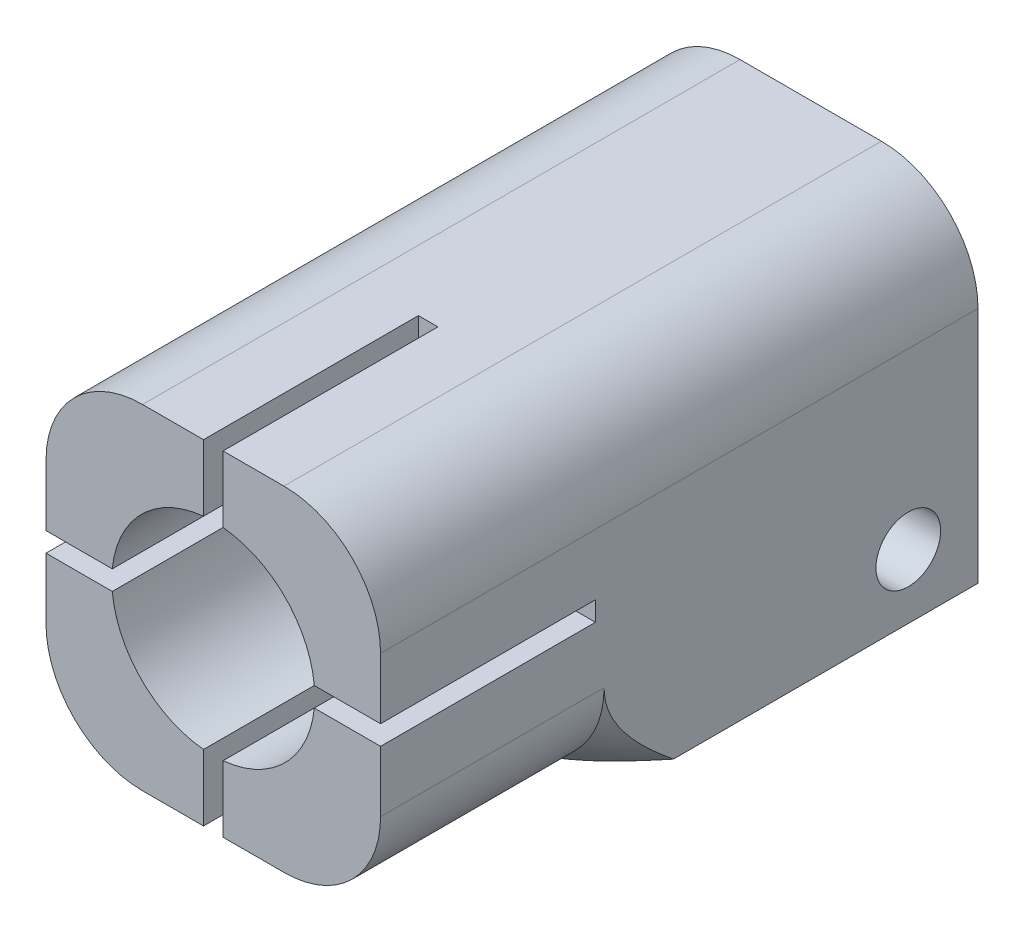
SolidWorks part; units mm, degrees
ref_plane "Front Plane" through (0, 0, 0) normal (0, 0, 1) x (1, 0, 0)
ref_plane "Top Plane" through (0, 0, 0) normal (0, 1, 0) x (1, 0, 0)
ref_plane "Right Plane" through (0, 0, 0) normal (1, 0, 0) x (0, 0, -1)
sketch "Sketch1" plane through (0, 0, 0) normal (0, 0, 1) x (1, 0, 0)
  line L1 (-3.55, 8.4) -> (3.55, 8.4)
  line L2 (-8.4, 3.55) -> (-8.4, -3.55)
  line L3 (-3.55, -8.4) -> (3.55, -8.4)
  line L4 (8.4, 3.55) -> (8.4, -3.55)
  line L5 (-8.4, 8.4) -> (8.4, -8.4) construction
  line L6 (-8.4, -8.4) -> (8.4, 8.4) construction
  arc A0 (3.55, 8.4) -> (8.4, 3.55) centre (3.55, 3.55) cw
  arc A1 (3.55, -8.4) -> (8.4, -3.55) centre (3.55, -3.55) ccw
  arc A2 (-8.4, -3.55) -> (-3.55, -8.4) centre (-3.55, -3.55) ccw
  arc A3 (-3.55, 8.4) -> (-8.4, 3.55) centre (-3.55, 3.55) ccw
  point P0 (0, 0)
  dimension "D2" = 4.85
  dimension "D1" = 16.8
extrude "Boss-Extrude1" add sketch "Sketch1" along normal blind 15
sketch "Sketch2" plane through (0, 0, 15) normal (0, 0, 1) x (1, 0, 0)
  line L0 (0, 5.095) -> (0, 8.4)
  line L1 (3.55, 8.4) -> (-3.55, 8.4) construction
  line L2 (0.49, 5.0714) -> (0.49, 8.4)
  line L3 (-0.49, 5.0714) -> (-0.49, 8.4)
  line L4 (-0.49, 8.4) -> (0.49, 8.4)
  line L5 (-0.49, 4.095) -> (-0.49, 8.4) construction
  line L6 (0, 4.095) -> (0, 8.4) construction
  line L7 (0.49, 4.095) -> (0.49, 8.4) construction
  line L8 (5.095, 0) -> (8.4, 0)
  line L9 (5.0714, -0.49) -> (8.4, -0.49)
  line L10 (5.0714, 0.49) -> (8.4, 0.49)
  line L11 (8.4, 0.49) -> (8.4, -0.49)
  line L12 (0, -5.095) -> (0, -8.4)
  line L13 (-0.49, -5.0714) -> (-0.49, -8.4)
  line L14 (0.49, -5.0714) -> (0.49, -8.4)
  line L15 (0.49, -8.4) -> (-0.49, -8.4)
  line L16 (-5.095, 0) -> (-8.4, 0)
  line L17 (-5.0714, 0.49) -> (-8.4, 0.49)
  line L18 (-5.0714, -0.49) -> (-8.4, -0.49)
  line L19 (-8.4, -0.49) -> (-8.4, 0.49)
  circle A0 centre (0, 0) radius 5.095
  arc A1 (-0.49, 5.0714) -> (0.49, 5.0714) centre (0, 0) cw
  arc A2 (5.0714, 0.49) -> (5.0714, -0.49) centre (0, 0) cw
  arc A3 (0.49, -5.0714) -> (-0.49, -5.0714) centre (0, 0) cw
  arc A4 (-5.0714, -0.49) -> (-5.0714, 0.49) centre (0, 0) cw
  point P36 (0, 0)
  dimension "D1" = 10.19
  dimension "D2" = 0.49
  dimension "D3" = 0.49
  dimension "D4" = 4
extrude "Cut-Extrude1" cut sketch "Sketch2" against normal blind 10.79 contours L2 L4 L3 A1 | L10 L11 L9 A2 | L14 L15 L13 A3 | L17 L19 L18 A4 | A0
sketch "Sketch4" plane through (0, 0, 0) normal (0, 0, -1) x (-1, 0, 0)
  line L0 (-8.4, -8.4) -> (-4, -8.4)
  line L1 (-4, -8.4) -> (-4, 4.9)
  line L2 (-4, 4.9) -> (4, 4.9)
  line L3 (0, 4.9) -> (0, 8.4)
  line L4 (-3.55, 8.4) -> (3.55, 8.4) construction
  line L5 (3.55, 8.4) -> (-3.55, 8.4)
  line L6 (-8.4, 3.55) -> (-8.4, -8.4)
  line L7 (0, 0) -> (0, 14.0769) construction
  line L8 (8.4, 3.55) -> (8.4, -8.4)
  line L9 (4, -8.4) -> (4, 4.9)
  line L10 (8.4, -8.4) -> (4, -8.4)
  line L11 (3.55, -8.4) -> (-3.55, -8.4) construction
  arc A0 (-3.55, 8.4) -> (-8.4, 3.55) centre (-3.55, 3.55) ccw
  arc A1 (3.55, 8.4) -> (8.4, 3.55) centre (3.55, 3.55) cw
  arc M13 (-3.55, 8.4) -> (-8.4, 3.55) centre (-3.55, 3.55) ccw
  line M14 (-8.4, 3.55) -> (-8.4, -3.55)
  arc M15 (-8.4, -3.55) -> (-3.55, -8.4) centre (-3.55, -3.55) ccw
  arc M17 (3.55, -8.4) -> (8.4, -3.55) centre (3.55, -3.55) ccw
  line M18 (8.4, -3.55) -> (8.4, 3.55)
  arc M19 (8.4, 3.55) -> (3.55, 8.4) centre (3.55, 3.55) ccw
  line M20 (3.55, 8.4) -> (-3.55, 8.4)
  dimension "D1" = 8
  dimension "D2" = 3.5
extrude "Boss-Extrude3" add sketch "Sketch4" along normal blind 15 contours L2 L3 L1 M20 M13 M14 M15 | L9 L3 L2 M17 M18 M19 M20 | L6 L0 L1 M15 | L10 L8 L9 M17 region at (7.3188, -7.316, 0) region at (5.2995, 1.1959, 0) region at (-5.2995, 1.1959, 0) region at (-7.3188, -7.316, 0)
ref_plane "Plane1" through (4, 0, 0) normal (-1, 0, 0) x (0, 0, 1)
sketch "Sketch7" plane through (8.4, 0, 0) normal (1, 0, 0) x (0, 0, -1)
  line L1 (-15, -3.55) -> (0, -3.55) construction
  line L2 (15, 3.55) -> (15, -8.4) construction
  circle A0 centre (11.5, -5.175) radius 1.625
  dimension "D1" = 3.25
  dimension "D2" = 3.5
extrude "Cut-Extrude2" cut sketch "Sketch7" against normal up to surface (16.8 mm away) contours A0 up to face at (-8.4, -1.68, 3.842)
chamfer "Chamfer2" distance 2.18 angle 60 2 edges at (-7.135, -6.8165, 0) (7.135, -6.8165, 0) first distance on face at (-6.4338, -7.3953, 0) first distance on face at (6.4338, -7.3953, 0)
